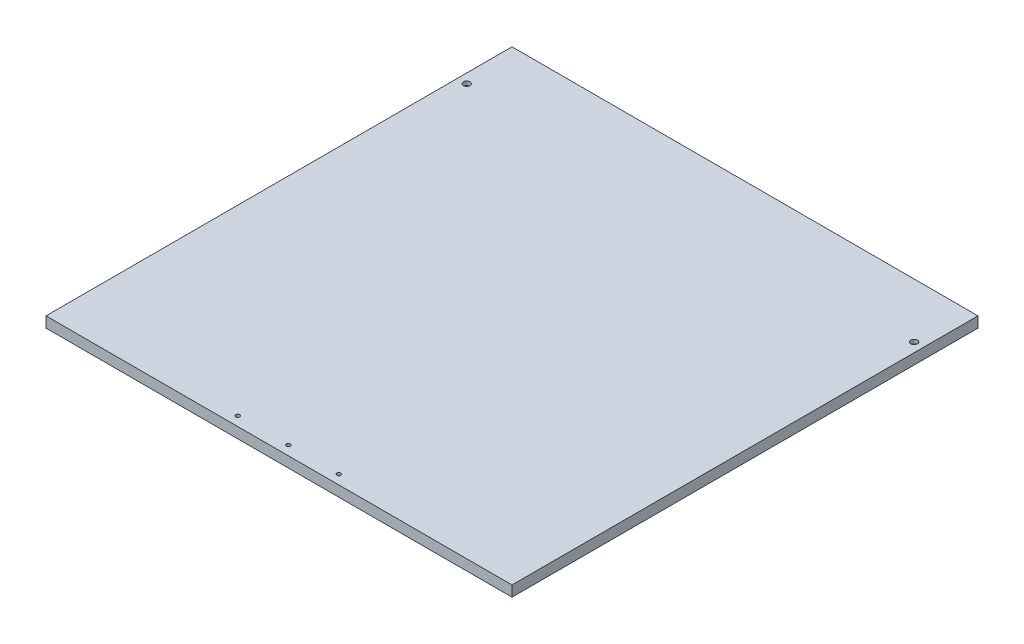
SolidWorks part; units mm, degrees
ref_plane "Front Plane" through (0, 0, 0) normal (0, 0, 1) x (1, 0, 0)
ref_plane "Top Plane" through (0, 0, 0) normal (0, 1, 0) x (1, 0, 0)
ref_plane "Right Plane" through (0, 0, 0) normal (1, 0, 0) x (0, 0, -1)
sketch "PlateSketch2" plane through (0, 0, 0) normal (0, 1, 0) x (1, 0, 0)
  line L1 (0, 0) -> (350, 0)
  line L2 (0, 0) -> (0, 350)
  line L3 (0, 350) -> (350, 350)
  line L4 (350, 0) -> (350, 350)
  circle A0 centre (7, 309) radius 1.5
  circle A1 centre (343, 309) radius 1.5
  circle A2 centre (137, 7) radius 1.5
  circle A3 centre (175, 7) radius 1.5
  circle A4 centre (213, 7) radius 1.5
  dimension "D5" = 3
  dimension "D10" = 3
  dimension "D1" = 350
  dimension "D2" = 350
  dimension "D3" = 7
  dimension "D4" = 7
  dimension "D6" = 41
  dimension "D7" = 38
  dimension "D8" = 38
  dimension "D9" = 175
  dimension "D11" = 7
extrude "Boss-Extrude1" add sketch "PlateSketch2" along normal blind 8
sketch "BoreSketch1" plane through (0, 8, 0) normal (0, 1, 0) x (1, 0, 0)
  circle A0 centre (7, 309) radius 2.5
  circle A1 centre (343, 309) radius 2.5
  circle A4 centre (7, 309) radius 1.5 construction
  circle A5 centre (343, 309) radius 1.5 construction
  dimension "D1" = 5
extrude "BoreCut-Extrude1" cut sketch "BoreSketch1" against normal blind 3
equation "\"BuildPlateStandoffHolesDistanceFromLeftOrRightSide\"= 7mm"
equation "\"BuildPlateStandoffHolesDistanceFromBackSide\"= 41mm"
equation "\"BedSpringHoleSize\"= 3mm"
equation "\"BuildPlateWidth\"= 350mm'Spec"
equation "\"BuildPlateLength\"= 350mm'Spec"
equation "\"D5@PlateSketch2\" = \"BedSpringHoleSize\""
equation "\"D10@PlateSketch2\" = \"BedSpringHoleSize\""
equation "\"BuildPlateBoreDiameter\"= 5mm'Spec"
equation "\"D1@BoreSketch1\" = \"BuildPlateBoreDiameter\""
equation "\"BuildPlateBoreDepth\"= 3mm'Spec"
equation "\"D1@BoreCut-Extrude1\" = \"BuildPlateBoreDepth\""
equation "\"BuildPlateDepth\"= 8mm'Spec"
equation "\"D1@Boss-Extrude1\"=\"BuildPlateDepth\""
equation "\"D1@PlateSketch2\"= \"BuildPlateLength\""
equation "\"D2@PlateSketch2\"=\"BuildPlateWidth\""
equation "\"D9@PlateSketch2\"=\"BuildPlateWidth\"/2"
equation "\"BuildPlateFlankingHoles\"= 38mm"
equation "\"D7@PlateSketch2\"=\"BuildPlateFlankingHoles\""
equation "\"D6@PlateSketch2\"=\"BuildPlateStandoffHolesDistanceFromBackSide\""
equation "\"D3@PlateSketch2\"=\"BuildPlateStandoffHolesDistanceFromLeftOrRightSide\""
equation "\"D4@PlateSketch2\"=\"BuildPlateStandoffHolesDistanceFromLeftOrRightSide\""
equation "\"BuildPlateStandoffHolesDistanceFromFront\"= 7mm"
equation "\"D11@PlateSketch2\"=\"BuildPlateStandoffHolesDistanceFromFront\""
